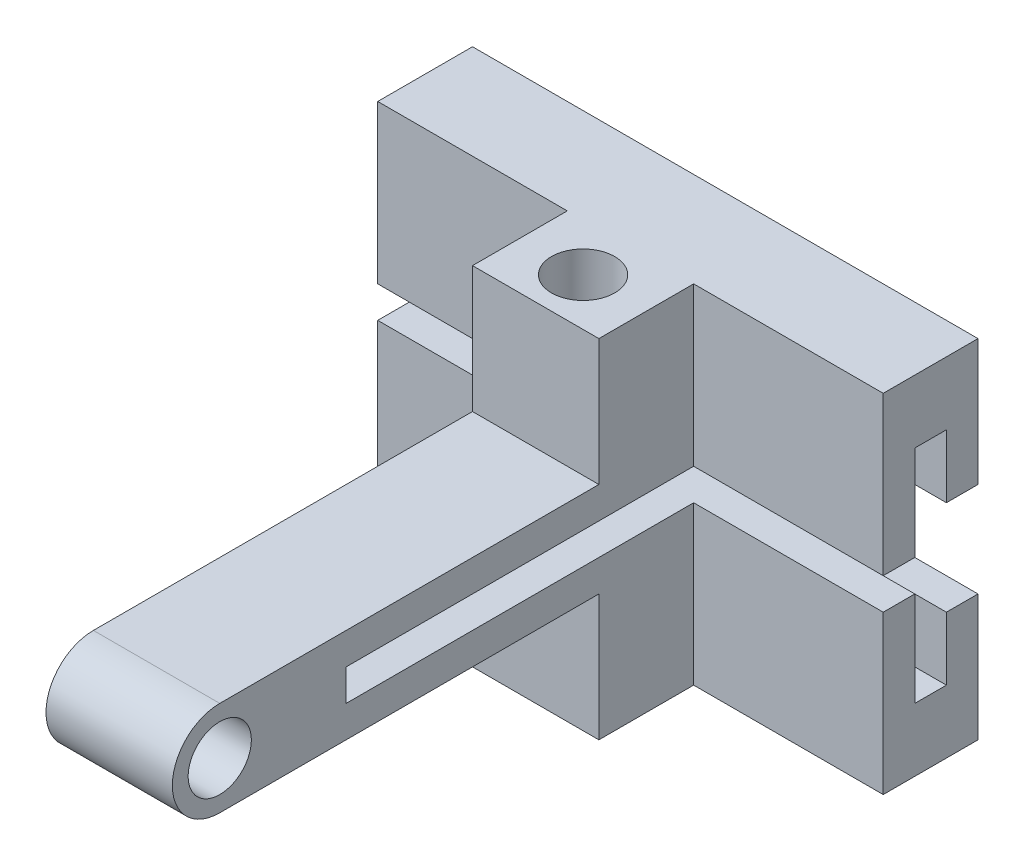
SolidWorks part; units mm, degrees
ref_plane "Front Plane" through (0, 0, 0) normal (1, 0, 0) x (0, 1, 0)
ref_plane "Top Plane" through (0, 0, 0) normal (0, 0, 1) x (0, 1, 0)
ref_plane "Right Plane" through (0, 0, 0) normal (0, 1, 0) x (-1, 0, 0)
sketch "Sketch1" plane through (0, 0, 0) normal (1, 0, 0) x (0, 1, 0)
  line L0 (-189.4407, 0) -> (201.5733, 0) construction
  line L1 (0, 136.4299) -> (0, -163.7335) construction
  line L10 (-15, 0) -> (-15, -120)
  line L11 (-15, -120) -> (-55, -120)
  line L12 (-55, -120) -> (-55, -150)
  line L13 (-55, -150) -> (-5, -150)
  line L14 (-5, -150) -> (-5, -40)
  line L15 (-5, -40) -> (5, -40)
  line L16 (55, -150) -> (5, -150)
  line L17 (55, -120) -> (55, -150)
  line L18 (15, -120) -> (55, -120)
  line L19 (5, -150) -> (5, -40)
  line L20 (15, 0) -> (15, -120)
  line L21 (-55, -150) -> (-55, -180)
  line L22 (-55, -180) -> (-15, -180)
  line L23 (-15, -180) -> (-15, -170)
  line L24 (-15, -170) -> (-35, -170)
  line L25 (-35, -170) -> (-35, -160)
  line L26 (-35, -160) -> (-5, -160)
  line L27 (-5, -160) -> (-5, -150)
  line L28 (55, -180) -> (15, -180)
  line L29 (15, -180) -> (15, -170)
  line L30 (15, -170) -> (35, -170)
  line L31 (35, -170) -> (35, -160)
  line L32 (35, -160) -> (5, -160)
  line L33 (55, -150) -> (55, -180)
  line L34 (5, -150) -> (5, -160)
  circle A2 centre (0, 0) radius 10
  circle A3 centre (0, 0) radius 15
  point P25 (-35, -165)
  point P26 (-20, -160)
  dimension "D10" = 10
  dimension "D11" = 30
  dimension "D5" = 50
  dimension "D6" = 10
  dimension "D1" = 20
  dimension "D2" = 30
  dimension "D3" = 120
  dimension "D4" = 30
  dimension "D7" = 30
  dimension "D8" = 110
  dimension "D9" = 40
  dimension "D12" = 10
extrude "Boss-Extrude1" add sketch "Sketch1" along normal mid plane 40 contours A3 L10 L11 L12 L13 L14 L15 L19 L16 L17 L18 L20 | A3 A2 region at (0, 0, -16.8601) region at (0, 0, 14.5757)
extrude "Boss-Extrude2" add sketch "Sketch1<3>" along normal mid plane 160 contours L16 L34 L32 L31 L30 L29 L28 L33 | L26 L27 L13 L21 L22 L23 L24 L25 region at (0, -30, -150.5831) region at (0, 54.4169, -165)
sketch "Sketch1<3>" plane through (0, 0, 0) normal (1, 0, 0) x (0, 1, 0) same geometry as "Sketch1"
sketch "Sketch2" plane through (0, 55, 0) normal (0, 1, 0) x (-1, 0, 0)
  line L0 (-20, -120) -> (-20, -150) construction
  circle A0 centre (0, -135) radius 10
  point P2 (0, 0)
  point P4 (0, 0)
  point P7 (-20, -135)
  dimension "D1" = 20
extrude "Cut-Extrude1" cut sketch "Sketch2" against normal through all both and the other way through all
